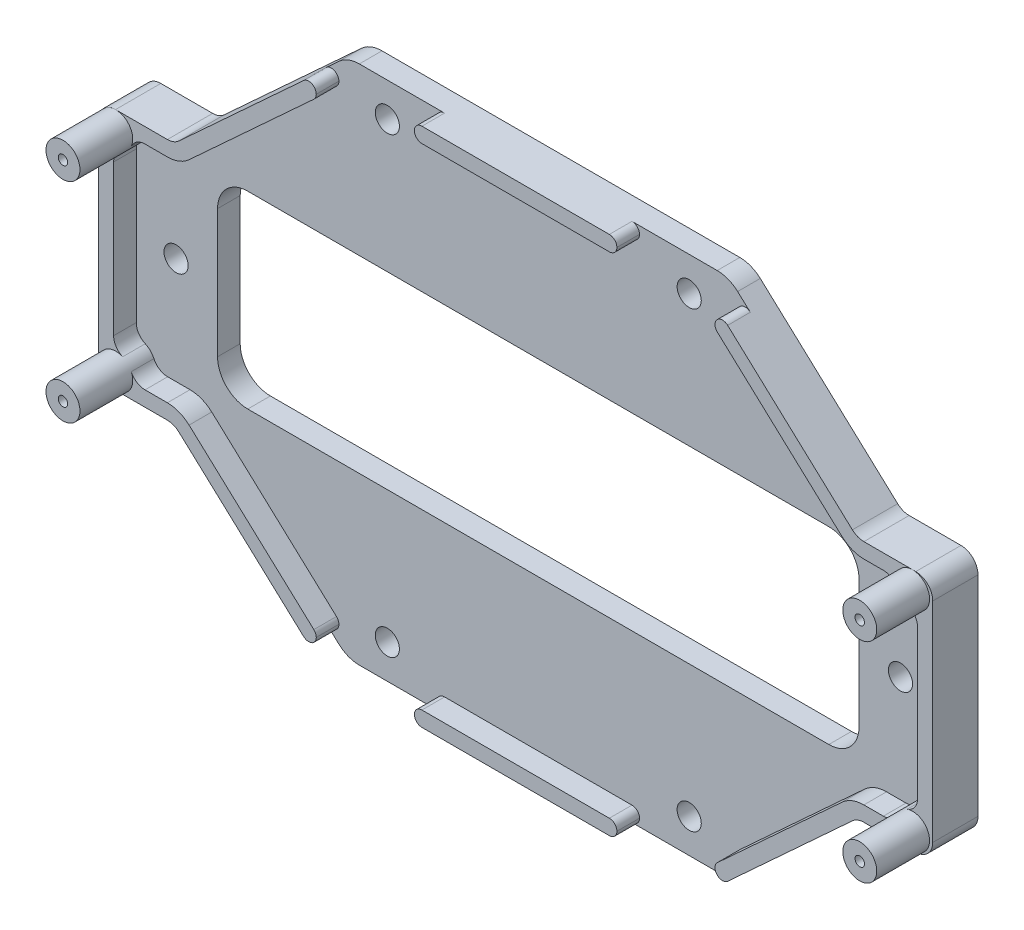
SolidWorks part; units mm, degrees
material "PLA"
ref_plane "Front Plane" through (0, 0, 0) normal (0, 0, 1) x (1, 0, 0)
ref_plane "Top Plane" through (0, 0, 0) normal (0, 1, 0) x (1, 0, 0)
ref_plane "Right Plane" through (0, 0, 0) normal (1, 0, 0) x (0, 0, -1)
sketch "Sketch1" plane through (0, 0, 0) normal (0, 0, 1) x (1, 0, 0)
  line L1 (0, 0) -> (110.54, 0)
  line L2 (0, 0) -> (0, 69)
  line L3 (0, 69) -> (110.54, 69)
  line L4 (110.54, 0) -> (110.54, 69)
  dimension "D1" = 69
  dimension "D2" = 110.54
extrude "Boss-Extrude1" add sketch "Sketch1" along normal blind 3
hole_wizard "Ø3.2 (3.2) Diameter Hole1" positions "Sketch3" profile "Sketch4" hole size "Ø3.2" standard "ISO" end condition through all
sketch "Sketch3" plane through (0, 0, 3) normal (0, 0, 1) x (1, 0, 0)
  point P0 (35.27, 64.5)
  point P3 (75.27, 64.5)
  point P6 (103.27, 34.5)
  point P9 (75.27, 4.5)
  point P12 (35.27, 4.5)
  point P15 (7.27, 34.5)
sketch "Sketch4" plane through (35.27, 64.5, 3) normal (1, 0, 0) x (0, -1, 0)
  line L0 (0, 0) -> (0, 3)
  line L1 (0, 3) -> (1.6, 3)
  line L2 (1.6, 3) -> (1.6, 0)
  line L5 (1.6, 0) -> (0, 0)
  line L11 (0, -6.35) -> (0, 107.95) construction
  dimension "Thru Hole Dia." = 3.2
  dimension "Thru Hole Depth" = 3
sketch "Sketch5" plane through (0, 0, 3) normal (0, 0, 1) x (1, 0, 0)
  circle A0 centre (2.2856, 48.3557) radius 2.25
  circle A1 centre (2.2856, 20.6443) radius 2.25
  circle A2 centre (107.8734, 48.3557) radius 2.25
  circle A3 centre (107.8734, 20.6443) radius 2.25
  dimension "D1" = 4.5
extrude "Boss-Extrude2" add sketch "Sketch5" along normal blind 10
sketch "Sketch6" plane through (0, 0, 3) normal (0, 0, 1) x (1, 0, 0)
  line L0 (12.77, 34.5) -> (0, 34.5) construction
  line L1 (16.77, 47) -> (93.77, 47)
  line L2 (12.77, 43) -> (12.77, 26)
  line L3 (16.77, 22) -> (93.77, 22)
  line L4 (97.77, 43) -> (97.77, 26)
  line L6 (55.27, 47) -> (55.27, 69) construction
  line L7 (110.54, 69) -> (0, 69) construction
  line L8 (0, 69) -> (0, 0) construction
  arc A0 (12.77, 26) -> (16.77, 22) centre (16.77, 26) ccw
  arc A1 (93.77, 22) -> (97.77, 26) centre (93.77, 26) ccw
  arc A2 (93.77, 47) -> (97.77, 43) centre (93.77, 43) cw
  arc A3 (16.77, 47) -> (12.77, 43) centre (16.77, 43) ccw
  dimension "D1" = 4
  dimension "D2" = 85
  dimension "D3" = 25
extrude "Cut-Extrude2" cut sketch "Sketch6" against normal through all
sketch "Sketch2" plane through (0, 0, 3) normal (0, 0, 1) x (1, 0, 0)
  line L1 (0, 69) -> (30, 69)
  line L2 (0, 69) -> (0, 50.6057)
  line L3 (0, 50.6057) -> (10, 50.6057)
  line L4 (30, 69) -> (10, 50.6057)
  line L6 (110.54, 69) -> (80.54, 69)
  line L7 (110.54, 69) -> (110.54, 50.6057)
  line L8 (110.54, 50.6057) -> (100.54, 50.6057)
  line L9 (80.54, 69) -> (100.54, 50.6057)
  line L10 (0, 0) -> (30, 0)
  line L11 (0, 0) -> (0, 18.3943)
  line L12 (0, 18.3943) -> (10, 18.3943)
  line L13 (30, 0) -> (10, 18.3943)
  line L15 (110.54, 0) -> (80.54, 0)
  line L16 (110.54, 0) -> (110.54, 18.3943)
  line L17 (110.54, 18.3943) -> (100.54, 18.3943)
  line L18 (80.54, 0) -> (100.54, 18.3943)
  line L19 (110.54, 69) -> (0, 69) construction
  circle A0 centre (2.2856, 48.3557) radius 2.25 construction
  circle A1 centre (2.2856, 20.6443) radius 2.25 construction
  circle A2 centre (107.8734, 20.6443) radius 2.25 construction
  circle A3 centre (107.8734, 48.3557) radius 2.25 construction
  dimension "D1" = 10
  dimension "D2" = 30
extrude "Cut-Extrude1" cut sketch "Sketch2" against normal through all
fillet "Fillet1" radius 2.25 8 edges at (0, 18.3943, 1.5) (10, 18.3943, 1.5) (110.54, 18.3943, 1.5) (100.54, 18.3943, 1.5) (110.54, 50.6057, 1.5) (100.54, 50.6057, 1.5) (10, 50.6057, 1.5) (0, 50.6057, 1.5)
fillet "Fillet3" radius 4 4 edges at (80.54, 0, 1.5) (30, 0, 1.5) (80.54, 69, 1.5) (30, 69, 1.5)
sketch "Sketch9" plane through (0, 0, 3) normal (0, 0, 1) x (1, 0, 0)
  line L76 (10.6458, 51.1996) -> (28.852, 67.9441) construction
  line L77 (2.2856, 50.6057) -> (9.1226, 50.6057) construction
  line L78 (2.25, 50.6057) -> (2.2856, 50.6057) construction
  line L79 (0, 48.3557) -> (0, 20.6443) construction
  line L80 (2.2856, 18.3943) -> (2.25, 18.3943) construction
  line L81 (9.1226, 18.3943) -> (2.2856, 18.3943) construction
  line L82 (28.852, 1.0559) -> (10.6458, 17.8004) construction
  line L83 (31.5597, 0) -> (78.9803, 0) construction
  line L84 (99.8942, 17.8004) -> (81.688, 1.0559) construction
  line L85 (107.8734, 18.3943) -> (101.4174, 18.3943) construction
  line L86 (108.29, 18.3943) -> (107.8734, 18.3943) construction
  line L87 (110.54, 20.6443) -> (110.54, 48.3557) construction
  line L88 (107.8734, 50.6057) -> (108.29, 50.6057) construction
  line L89 (101.4174, 50.6057) -> (107.8734, 50.6057) construction
  line L90 (81.688, 67.9441) -> (99.8942, 51.1996) construction
  line L91 (78.9803, 69) -> (31.5597, 69) construction
  line L92 (10.6458, 51.1996) -> (28.852, 67.9441)
  line L93 (2.2856, 50.6057) -> (9.1226, 50.6057)
  line L94 (2.25, 50.6057) -> (2.2856, 50.6057)
  line L95 (0, 48.3557) -> (0, 20.6443)
  line L96 (2.2856, 18.3943) -> (2.25, 18.3943)
  line L97 (9.1226, 18.3943) -> (2.2856, 18.3943)
  line L98 (28.852, 1.0559) -> (10.6458, 17.8004)
  line L99 (31.5597, 0) -> (78.9803, 0)
  line L100 (99.8942, 17.8004) -> (81.688, 1.0559)
  line L101 (107.8734, 18.3943) -> (101.4174, 18.3943)
  line L102 (108.29, 18.3943) -> (107.8734, 18.3943)
  line L103 (110.54, 20.6443) -> (110.54, 48.3557)
  line L104 (107.8734, 50.6057) -> (108.29, 50.6057)
  line L105 (101.4174, 50.6057) -> (107.8734, 50.6057)
  line L106 (81.688, 67.9441) -> (99.8942, 51.1996)
  line L107 (78.9803, 69) -> (31.5597, 69)
  line L108 (11.9997, 49.7275) -> (30.2059, 66.4721)
  line L109 (2.2856, 48.6057) -> (9.1226, 48.6057)
  line L110 (2.25, 48.6057) -> (2.2856, 48.6057)
  line L111 (2, 48.3557) -> (2, 20.6443)
  line L112 (2.2856, 20.3943) -> (2.25, 20.3943)
  line L113 (9.1226, 20.3943) -> (2.2856, 20.3943)
  line L114 (30.2059, 2.5279) -> (11.9997, 19.2725)
  line L115 (31.5597, 2) -> (78.9803, 2)
  line L116 (98.5403, 19.2725) -> (80.3341, 2.5279)
  line L117 (107.8734, 20.3943) -> (101.4174, 20.3943)
  line L118 (108.29, 20.3943) -> (107.8734, 20.3943)
  line L119 (108.54, 20.6443) -> (108.54, 48.3557)
  line L120 (107.8734, 48.6057) -> (108.29, 48.6057)
  line L121 (101.4174, 48.6057) -> (107.8734, 48.6057)
  line L122 (80.3341, 66.4721) -> (98.5403, 49.7275)
  line L123 (78.9803, 67) -> (31.5597, 67)
  arc A68 (31.5597, 69) -> (28.852, 67.9441) centre (31.5597, 65) ccw construction
  arc A69 (9.1226, 50.6057) -> (10.6458, 51.1996) centre (9.1226, 52.8557) ccw construction
  arc A70 (2.25, 50.6057) -> (0, 48.3557) centre (2.25, 48.3557) ccw construction
  arc A71 (0, 20.6443) -> (2.25, 18.3943) centre (2.25, 20.6443) ccw construction
  arc A72 (10.6458, 17.8004) -> (9.1226, 18.3943) centre (9.1226, 16.1443) ccw construction
  arc A73 (28.852, 1.0559) -> (31.5597, 0) centre (31.5597, 4) ccw construction
  arc A74 (78.9803, 0) -> (81.688, 1.0559) centre (78.9803, 4) ccw construction
  arc A75 (101.4174, 18.3943) -> (99.8942, 17.8004) centre (101.4174, 16.1443) ccw construction
  arc A76 (108.29, 18.3943) -> (110.54, 20.6443) centre (108.29, 20.6443) ccw construction
  arc A77 (110.54, 48.3557) -> (108.29, 50.6057) centre (108.29, 48.3557) ccw construction
  arc A78 (99.8942, 51.1996) -> (101.4174, 50.6057) centre (101.4174, 52.8557) ccw construction
  arc A79 (81.688, 67.9441) -> (78.9803, 69) centre (78.9803, 65) ccw construction
  arc A84 (31.5597, 69) -> (28.852, 67.9441) centre (31.5597, 65) ccw
  arc A85 (9.1226, 50.6057) -> (10.6458, 51.1996) centre (9.1226, 52.8557) ccw
  arc A86 (2.25, 50.6057) -> (0, 48.3557) centre (2.25, 48.3557) ccw
  arc A87 (0, 20.6443) -> (2.25, 18.3943) centre (2.25, 20.6443) ccw
  arc A88 (10.6458, 17.8004) -> (9.1226, 18.3943) centre (9.1226, 16.1443) ccw
  arc A89 (28.852, 1.0559) -> (31.5597, 0) centre (31.5597, 4) ccw
  arc A90 (78.9803, 0) -> (81.688, 1.0559) centre (78.9803, 4) ccw
  arc A91 (101.4174, 18.3943) -> (99.8942, 17.8004) centre (101.4174, 16.1443) ccw
  arc A92 (108.29, 18.3943) -> (110.54, 20.6443) centre (108.29, 20.6443) ccw
  arc A93 (110.54, 48.3557) -> (108.29, 50.6057) centre (108.29, 48.3557) ccw
  arc A94 (99.8942, 51.1996) -> (101.4174, 50.6057) centre (101.4174, 52.8557) ccw
  arc A95 (81.688, 67.9441) -> (78.9803, 69) centre (78.9803, 65) ccw
  arc A96 (31.5597, 67) -> (30.2059, 66.4721) centre (31.5597, 65) ccw
  arc A97 (9.1226, 48.6057) -> (11.9997, 49.7275) centre (9.1226, 52.8557) ccw
  arc A98 (2.25, 48.6057) -> (2, 48.3557) centre (2.25, 48.3557) ccw
  arc A99 (2, 20.6443) -> (2.25, 20.3943) centre (2.25, 20.6443) ccw
  arc A100 (11.9997, 19.2725) -> (9.1226, 20.3943) centre (9.1226, 16.1443) ccw
  arc A101 (30.2059, 2.5279) -> (31.5597, 2) centre (31.5597, 4) ccw
  arc A102 (78.9803, 2) -> (80.3341, 2.5279) centre (78.9803, 4) ccw
  arc A103 (101.4174, 20.3943) -> (98.5403, 19.2725) centre (101.4174, 16.1443) ccw
  arc A104 (108.29, 20.3943) -> (108.54, 20.6443) centre (108.29, 20.6443) ccw
  arc A105 (108.54, 48.3557) -> (108.29, 48.6057) centre (108.29, 48.3557) ccw
  arc A106 (98.5403, 49.7275) -> (101.4174, 48.6057) centre (101.4174, 52.8557) ccw
  arc A107 (80.3341, 66.4721) -> (78.9803, 67) centre (78.9803, 65) ccw
  dimension "D1" = 2
extrude "Boss-Extrude3" add sketch "Sketch9" along normal blind 3
hole_wizard "M1.6 Tapped Hole1" positions "Sketch7" profile "Sketch8" tap size "M1.6" standard "ISO" end condition through all
sketch "Sketch7" plane through (0, 0, 13) normal (0, 0, 1) x (1, 0, 0)
  point P0 (2.2856, 48.3557)
  point P3 (2.2856, 20.6443)
  point P6 (107.8734, 48.3557)
  point P9 (107.8734, 20.6443)
sketch "Sketch8" plane through (2.2856, 48.3557, 13) normal (1, 0, 0) x (0, -1, 0)
  line L0 (0, 0) -> (0, 13)
  line L1 (0, 13) -> (0.625, 13)
  line L2 (0.625, 13) -> (0.625, 0)
  line L5 (0.625, 0) -> (0, 0)
  line L11 (0, -6.35) -> (0, 107.95) construction
  dimension "Thru Tap Drill Dia." = 1.25
  dimension "Thru Tap Drill Depth" = 13
cosmetic thread "Hole Thread1" parameters "D2"=1.6
cosmetic thread "Hole Thread2" parameters "D2"=1.6
cosmetic thread "Hole Thread3" parameters "D2"=1.6
cosmetic thread "Hole Thread4" parameters "D2"=1.6
fillet "Fillet2" radius 2 8 edges at (105.6373, 48.6057, 4.5) (108.54, 46.2067, 4.5) (108.54, 22.7933, 4.5) (105.6373, 20.3943, 4.5) (4.5217, 20.3943, 4.5) (2, 22.8761, 4.5) (2, 46.1239, 4.5) (4.5217, 48.6057, 4.5)
sketch "Sketch10" plane through (0, 0, 6) normal (0, 0, 1) x (1, 0, 0)
  line L0 (31.5597, 0) -> (78.9803, 0) construction
  line L1 (28.852, 69) -> (41.852, 69)
  line L2 (28.852, 69) -> (28.852, 0)
  line L3 (28.852, 0) -> (41.852, 0)
  line L4 (81.688, 69) -> (81.688, 0)
  line L5 (78.9803, 69) -> (31.5597, 69) construction
  line L6 (68.688, 69) -> (81.688, 69)
  line L8 (41.852, 69) -> (41.852, 0)
  line L10 (68.688, 69) -> (68.688, 0)
  line L11 (68.688, 0) -> (81.688, 0)
  dimension "D1" = 13
extrude "Cut-Extrude3" cut sketch "Sketch10" against normal up to surface (3 mm away) up to face at (55.27, 34.5, 3)
fillet "Fillet4" radius 1 16 edges at (81.688, 3.7731, 4.5) (41.852, 0, 4.5) (41.852, 2, 4.5) (68.688, 0, 4.5) (68.688, 2, 4.5) (81.688, 1.0559, 4.5) (28.852, 1.0559, 4.5) (28.852, 3.7731, 4.5) (28.852, 65.2269, 4.5) (28.852, 67.9441, 4.5) (81.688, 65.2269, 4.5) (81.688, 67.9441, 4.5) (68.688, 67, 4.5) (68.688, 69, 4.5) (41.852, 69, 4.5) (41.852, 67, 4.5)
